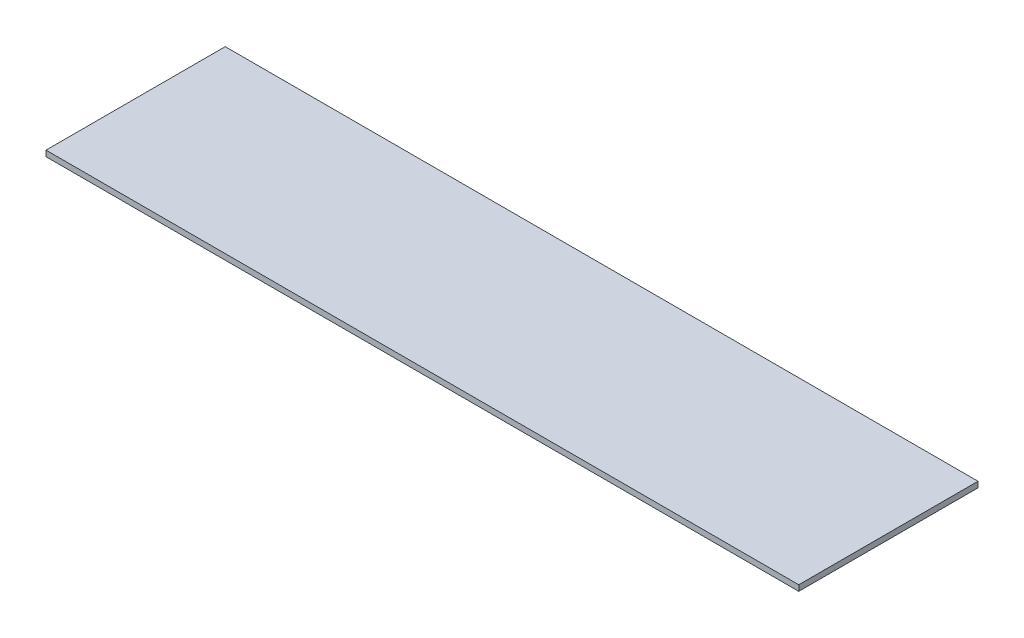
SolidWorks part; units mm, degrees
material "PE High Density"
ref_plane "Front Plane" through (0, 0, 0) normal (0, 0, 1) x (1, 0, 0)
ref_plane "Top Plane" through (0, 0, 0) normal (0, 1, 0) x (1, 0, 0)
ref_plane "Right Plane" through (0, 0, 0) normal (1, 0, 0) x (0, 0, -1)
other "Bounding Box"
ref_plane "Default Plane" through (0, 2.286, 19.05) normal (0, -1, 0) x (-1, 0, 0)
sketch "Sketch1" plane through (0, 0, 0) normal (0, 1, 0) x (1, 0, 0)
  line L1 (-66.675, -15.875) -> (66.675, -15.875)
  line L2 (-66.675, -15.875) -> (-66.675, 15.875)
  line L3 (-66.675, 15.875) -> (66.675, 15.875)
  line L4 (66.675, -15.875) -> (66.675, 15.875)
  line L5 (-66.675, -15.875) -> (66.675, 15.875) construction
  line L6 (-66.675, 15.875) -> (66.675, -15.875) construction
  point P0 (0, 0)
  dimension "D1" = 133.35
  dimension "D2" = 31.75
extrude "Boss-Extrude1" add sketch "Sketch1" along normal mid plane 1.016
equation "\"Unit Measure\"= \"BoundingVolume\" / \"Thickness\"'in^2"
